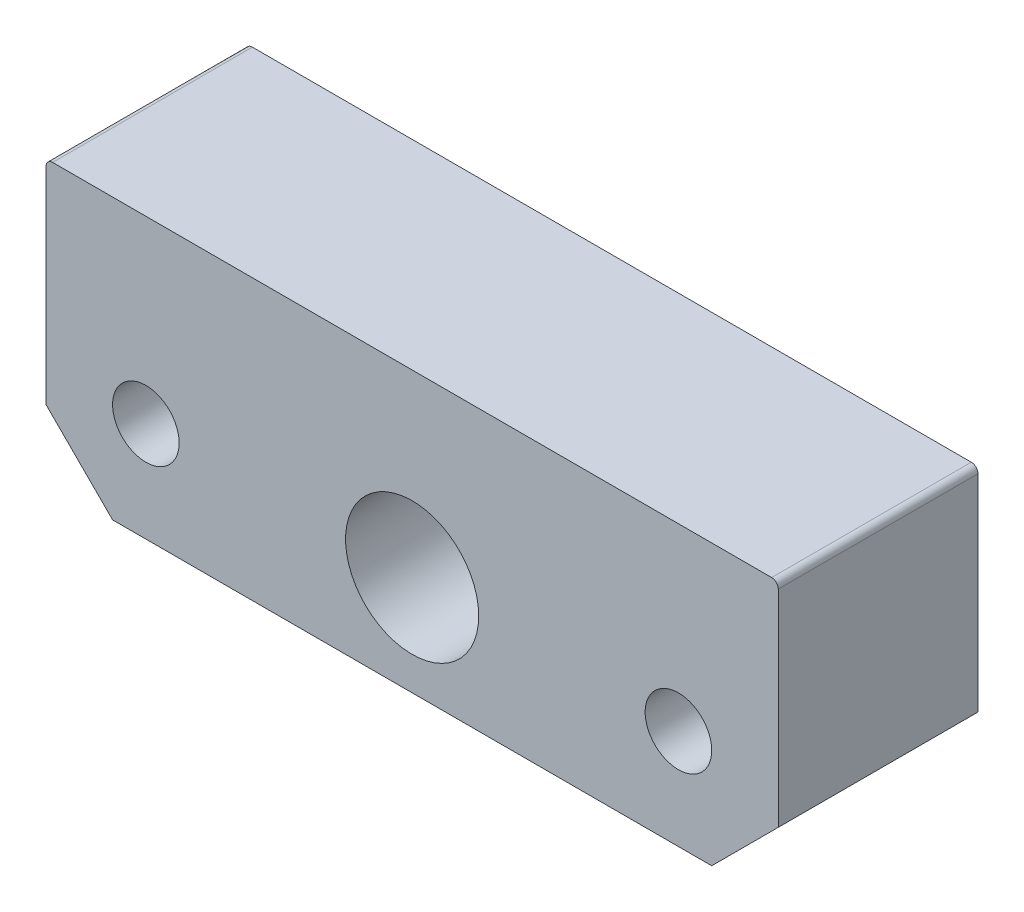
SolidWorks part; units mm, degrees
ref_plane "Alzado" through (0, 0, 0) normal (0, 0, 1) x (1, 0, 0)
ref_plane "Planta" through (0, 0, 0) normal (0, 1, 0) x (1, 0, 0)
ref_plane "Vista lateral" through (0, 0, 0) normal (1, 0, 0) x (0, 0, -1)
sketch "Croquis1" plane through (0, 0, 0) normal (0, 0, 1) x (1, 0, 0)
  line L1 (-55, -21) -> (55, -21)
  line L2 (-55, -21) -> (-55, 21)
  line L3 (-55, 21) -> (55, 21)
  line L4 (55, -21) -> (55, 21)
  line L5 (-55, -21) -> (55, 21) construction
  line L6 (-55, 21) -> (55, -21) construction
  point P0 (0, 0)
  dimension "D1" = 42
  dimension "D2" = 110
extrude "Saliente-Extruir1" add sketch "Croquis1" along normal blind 30
chamfer "Chaflán1" distance 10 angle 45 2 edges at (-55, -21, 15) (55, -21, 15)
fillet "Redondeo1" radius 1 2 edges at (-55, 21, 15) (55, 21, 15)
sketch "Croquis2" plane through (0, 0, 30) normal (0, 0, 1) x (1, 0, 0)
  line L0 (-40, -6) -> (40, -6) construction
  line L1 (54, 21) -> (-54, 21) construction
  circle A0 centre (-40, -6) radius 5
  circle A1 centre (40, -6) radius 5
  circle A2 centre (0, -6) radius 10
  point P4 (0, -6)
  point P9 (0, 0)
  point P10 (0, 0)
  point P11 (0, 0)
  point P12 (10.6237, -11.4439)
  point P13 (0, 0)
  point P14 (0, -6.2924)
  dimension "D2" = 10
  dimension "D3" = 20
  dimension "D1" = 80
  dimension "D4" = 27
extrude "Cortar-Extruir1" cut sketch "Croquis2" against normal blind 30
